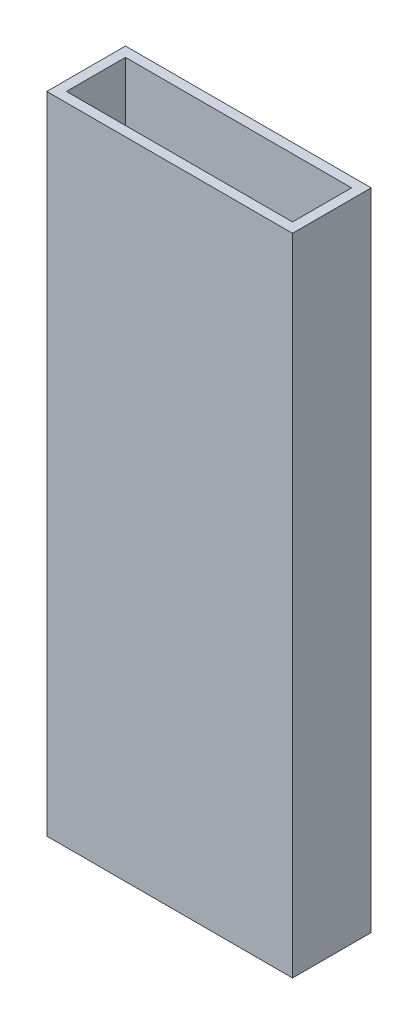
SolidWorks part; units mm, degrees
ref_plane "Front Plane" through (0, 0, 0) normal (0, 0, 1) x (1, 0, 0)
ref_plane "Top Plane" through (0, 0, 0) normal (0, 1, 0) x (1, 0, 0)
ref_plane "Right Plane" through (0, 0, 0) normal (1, 0, 0) x (0, 0, -1)
sketch "Sketch1" plane through (0, 0, 0) normal (0, 1, 0) x (1, 0, 0)
  line L0 (0, 9.152) -> (0, 12.2) construction
  line L1 (-38.1, 12.2) -> (38.1, 12.2)
  line L2 (-38.1, 12.2) -> (-38.1, -12.2)
  line L3 (-38.1, -12.2) -> (38.1, -12.2)
  line L4 (38.1, 12.2) -> (38.1, -12.2)
  line L5 (-35.052, 9.152) -> (35.052, 9.152)
  line L6 (-35.052, 9.152) -> (-35.052, -9.152)
  line L7 (-35.052, -9.152) -> (35.052, -9.152)
  line L8 (35.052, 9.152) -> (35.052, -9.152)
  line L9 (35.052, 0) -> (38.1, 0) construction
  line L10 (0, -9.152) -> (0, -12.2) construction
  line L11 (-35.052, 0) -> (-38.1, 0) construction
  line L12 (0, 9.152) -> (0, 0) construction
  line L13 (0, 0) -> (-35.052, 0) construction
  dimension "D1" = 76.2
  dimension "D2" = 24.4
  dimension "D3" = 3.048
extrude "Boss-Extrude1" add sketch "Sketch1" along normal blind 200
ref_plane "Plane1" through (0, 0, 0) normal (0, 0, 1) x (1, 0, 0)
sketch "Sketch2" plane through (0, 0, 0) normal (0, 0, 1) x (1, 0, 0)
  line L0 (0, 0) -> (0, 200) construction
  line L1 (-38.1, 200) -> (38.1, 200) construction
  line L2 (0, 100) -> (-38.1, 100) construction
  line L3 (-38.1, 200) -> (-38.1, 0) construction
  line L4 (0, 100) -> (38.1, 100) construction
  line L5 (38.1, 200) -> (38.1, 0) construction
ref_axis "Axis1" through (0, 200, 0) along (0, -1, 0)
equation "\"tubeMainWidth\" = 76.2mm"
equation "\"tubeSecondWidth\" = 24.4mm"
equation "\"tubeThickness\" = 3.048mm"
equation "\"halfMainWidthOfTubing\" = (\"tubeMainWidth\"/2)"
equation "\"D1@Sketch1\"=\"tubeMainWidth\""
equation "\"D2@Sketch1\"=\"tubeSecondWidth\""
equation "\"D3@Sketch1\"=\"tubeThickness\""
